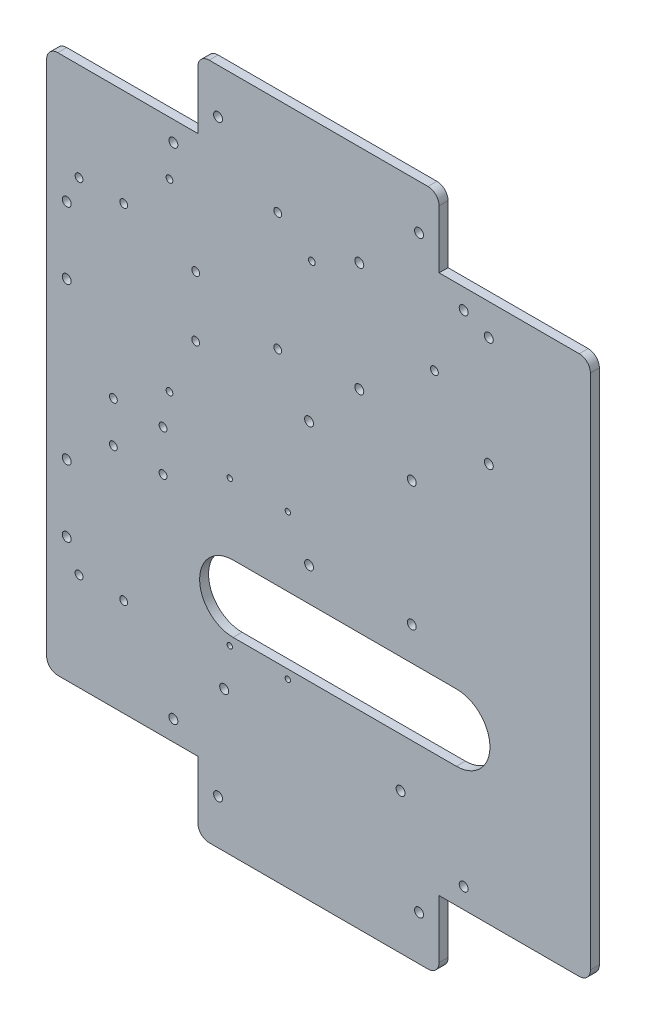
SolidWorks part; units mm, degrees
material "Alliage 1060"
ref_plane "Plan de dessus" through (0, 0, 0) normal (0, 0, 1) x (1, 0, 0)
ref_plane "Plan de droite" through (0, 0, 0) normal (0, 1, 0) x (1, 0, 0)
ref_plane "Plan de face" through (0, 0, 0) normal (1, 0, 0) x (0, 0, -1)
sketch "Esquisse1" plane through (0, 0, 0) normal (0, 0, 1) x (1, 0, 0)
  line L0 (0, 0) -> (-200, 0)
  line L1 (-200, 0) -> (-224.7487, 24.7487)
  line L2 (-224.7487, 24.7487) -> (-224.7487, 284.7487)
  line L3 (-224.7487, 284.7487) -> (-200, 309.4975)
  line L4 (-200, 309.4975) -> (0, 309.4975)
  line L5 (0, 309.4975) -> (24.7487, 284.7487)
  line L6 (24.7487, 284.7487) -> (24.7487, 24.7487)
  line L7 (24.7487, 24.7487) -> (0, 0)
  dimension "D1" = 260
  dimension "D2" = 35
  dimension "D3" = 135
  dimension "D4" = 200
extrude "Base" add sketch "Esquisse1" along normal blind 4
fillet "Congé1" radius 3 8 edges at (-200, 0, 2) (-224.7487, 24.7487, 2) (-224.7487, 284.7487, 2) (-200, 309.4975, 2) (0, 309.4975, 2) (24.7487, 284.7487, 2) (24.7487, 24.7487, 2) (0, 0, 2)
sketch "Esquisse19" plane through (0, 0, 0) normal (0, 0, -1) x (-1, 0, 0)
  line L0 (100, 309.4975) -> (100, 0) construction
  line L1 (1.2426, 309.4975) -> (198.7574, 309.4975) construction
  line L2 (198.7574, 0) -> (1.2426, 0) construction
  line L3 (-24.7487, 154.7487) -> (224.7487, 154.7487) construction
  line L4 (-24.7487, 25.9914) -> (-24.7487, 283.5061) construction
  line L5 (224.7487, 283.5061) -> (224.7487, 25.9914) construction
sketch "Esquisse25" plane through (0, 0, 0) normal (0, 0, -1) x (-1, 0, 0)
  line L0 (-24.7487, 25.9914) -> (-24.7487, 283.5061) construction
  line L1 (-21.7487, 33) -> (45, 33)
  line L2 (-24.7487, 33) -> (-24.7487, 0)
  line L3 (-24.7487, 0) -> (45, 0)
  line L4 (45, 33) -> (45, 3)
  line L5 (198.7574, 0) -> (1.2426, 0) construction
  line L6 (100, 309.4975) -> (100, 0) construction
  line L7 (100, 0) -> (100, 309.4975) construction
  line L8 (-24.7487, 154.7487) -> (224.7487, 154.7487) construction
  line L9 (224.7487, 0) -> (155, 0)
  line L10 (155, 33) -> (155, 3)
  line L11 (221.7487, 33) -> (155, 33)
  line L12 (224.7487, 33) -> (224.7487, 0)
  line L13 (224.7487, 276.4975) -> (224.7487, 309.4975)
  line L14 (221.7487, 276.4975) -> (155, 276.4975)
  line L15 (155, 276.4975) -> (155, 306.4975)
  line L16 (224.7487, 309.4975) -> (155, 309.4975)
  line L17 (-24.7487, 309.4975) -> (45, 309.4975)
  line L18 (45, 276.4975) -> (45, 306.4975)
  line L19 (-21.7487, 276.4975) -> (45, 276.4975)
  line L20 (-24.7487, 276.4975) -> (-24.7487, 309.4975)
  line L22 (45, 309.4975) -> (155, 309.4975)
  line L24 (45, 306.4975) -> (155, 306.4975)
  line L26 (45, 0) -> (155, 0)
  line L28 (45, 3) -> (155, 3)
  line L31 (-24.7487, 276.4975) -> (-24.7487, 33)
  line L33 (-21.7487, 276.4975) -> (-21.7487, 33)
  line L35 (224.7487, 276.4975) -> (224.7487, 33)
  line L37 (221.7487, 276.4975) -> (221.7487, 33)
  dimension "D1" = 55
  dimension "D2" = 33
  dimension "D3" = 3
  dimension "D4" = 3
  dimension "D5" = 3
  dimension "D6" = 3
extrude "Enlèv. mat.-Extru.1" cut sketch "Esquisse25" against normal through all
sketch "Esquisse33" plane through (0, 0, 4) normal (0, 0, 1) x (1, 0, 0)
  line L0 (-207.2487, 231.7487) -> (-187.2487, 231.7487) construction
  line L2 (-221.7487, 33) -> (-221.7487, 276.4975) construction
  line L3 (-221.7487, 154.7487) -> (21.7487, 154.7487) construction
  line L4 (21.7487, 276.4975) -> (21.7487, 33) construction
  line L5 (-100, 306.4975) -> (-100, 3) construction
  line L6 (-155, 306.4975) -> (-45, 306.4975) construction
  line L7 (-45, 3) -> (-155, 3) construction
  circle A0 centre (-207.2487, 231.7487) radius 1.75
  circle A1 centre (-187.2487, 231.7487) radius 1.75
  circle A2 centre (-207.2487, 77.7487) radius 1.75
  circle A3 centre (-187.2487, 77.7487) radius 1.75
  dimension "D3" = 3.5
  dimension "D1" = 20
  dimension "D2" = 14.5
  dimension "D4" = 77
extrude "Percage Main_De_Dieu" cut sketch "Esquisse33" against normal through all
sketch "Esquisse26" plane through (0, 0, 0) normal (0, 0, -1) x (-1, 0, 0)
  line L0 (212.7487, 189.7487) -> (212.7487, 219.7487) construction
  line L1 (221.7487, 33) -> (221.7487, 276.4975) construction
  line L2 (-24.7487, 154.7487) -> (224.7487, 154.7487) construction
  line L3 (224.7487, 154.7487) -> (-24.7487, 154.7487) construction
  line L4 (100, 309.4975) -> (100, 0) construction
  circle A0 centre (212.7487, 189.7487) radius 2
  circle A1 centre (212.7487, 219.7487) radius 2
  circle A2 centre (212.7487, 89.7487) radius 2
  circle A3 centre (212.7487, 119.7487) radius 2
  point P8 (212.7487, 204.7487)
  dimension "D1" = 4
  dimension "D2" = 30
  dimension "D3" = 9
  dimension "D4" = 50
extrude "Percage Buck Converter" cut sketch "Esquisse26" against normal through all
sketch "Esquisse27" plane through (0, 0, 0) normal (0, 0, -1) x (-1, 0, 0)
  line L0 (142.2513, 66) -> (63.2513, 66) construction
  line L1 (-21.7487, 276.4975) -> (-21.7487, 33) construction
  line L2 (-21.7487, 33) -> (45, 33) construction
  circle A0 centre (142.2513, 66) radius 2
  circle A1 centre (63.2513, 66) radius 2
  dimension "D2" = 4
  dimension "D1" = 79
  dimension "D3" = 85
  dimension "D4" = 33
extrude "Percage Teensy Moteur" cut sketch "Esquisse27" against normal through all
sketch "Esquisse28" plane through (0, 0, 0) normal (0, 0, -1) x (-1, 0, 0)
  line L0 (166.7487, 169.0225) -> (166.7487, 251.4975) construction
  line L1 (166.7487, 251.4975) -> (102.9987, 251.4975) construction
  line L2 (224.7487, 154.7487) -> (-24.7487, 154.7487) construction
  line L3 (221.7487, 33) -> (221.7487, 276.4975) construction
  line L4 (221.7487, 276.4975) -> (155, 276.4975) construction
  circle A0 centre (166.7487, 251.4975) radius 1.5
  circle A1 centre (102.9987, 251.4975) radius 1.5
  circle A2 centre (166.7487, 169.0225) radius 1.5
  dimension "D1" = 3
  dimension "D2" = 63.75
  dimension "D3" = 82.475
  dimension "D4" = 55
  dimension "D5" = 25
extrude "Percage Carte Alim" cut sketch "Esquisse28" against normal through all
sketch "Esquisse29" plane through (0, 0, 0) normal (0, 0, -1) x (-1, 0, 0)
  line L0 (221.7487, 33) -> (221.7487, 276.4975) construction
  line L1 (81.7487, 212.4975) -> (23.7487, 212.4975) construction
  line L2 (81.7487, 212.4975) -> (81.7487, 261.4975) construction
  line L3 (81.7487, 261.4975) -> (23.7487, 261.4975) construction
  line L4 (23.7487, 212.4975) -> (23.7487, 261.4975) construction
  line L5 (221.7487, 276.4975) -> (155, 276.4975) construction
  circle A0 centre (81.7487, 212.4975) radius 2
  circle A1 centre (23.7487, 212.4975) radius 2
  circle A2 centre (23.7487, 261.4975) radius 2
  circle A3 centre (81.7487, 261.4975) radius 2
  dimension "D3" = 4
  dimension "D1" = 49
  dimension "D2" = 58
  dimension "D4" = 140
  dimension "D5" = 15
extrude "Percage Rasp" cut sketch "Esquisse29" against normal through all
sketch "Esquisse32" plane through (0, 0, 4) normal (0, 0, 1) x (1, 0, 0)
  line L0 (-118.2513, 262.8275) -> (-118.2513, 209.8275) construction
  line L1 (-48.1113, 236.4975) -> (-118.2513, 236.4975) construction
  line L2 (-45, 276.4975) -> (21.7487, 276.4975) construction
  line L3 (21.7487, 276.4975) -> (21.7487, 33) construction
  circle A0 centre (-118.2513, 262.8275) radius 1.75
  circle A1 centre (-118.2513, 209.8275) radius 1.75
  circle A2 centre (-48.1113, 236.4975) radius 1.75
  dimension "D1" = 3.5
  dimension "D2" = 53
  dimension "D3" = 70.14
  dimension "D4" = 26.33
  dimension "D5" = 40
  dimension "D6" = 140
extrude "Percage Teensy Actionneurs" cut sketch "Esquisse32" against normal through all
sketch "Esquisse30" plane through (0, 0, 0) normal (0, 0, -1) x (-1, 0, 0)
  line L0 (-21.7487, 276.4975) -> (-21.7487, 33) construction
  line L1 (104.2513, 133) -> (58.2513, 133) construction
  line L2 (104.2513, 133) -> (104.2513, 188.8) construction
  line L3 (104.2513, 188.8) -> (58.2513, 188.8) construction
  line L4 (58.2513, 133) -> (58.2513, 188.8) construction
  line L5 (-21.7487, 33) -> (45, 33) construction
  circle A0 centre (104.2513, 133) radius 2
  circle A1 centre (58.2513, 133) radius 2
  circle A2 centre (58.2513, 188.8) radius 2
  circle A3 centre (104.2513, 188.8) radius 2
  dimension "D3" = 4
  dimension "D1" = 55.8
  dimension "D2" = 46
  dimension "D4" = 80
  dimension "D5" = 100
extrude "Percage Alim Actionneurs" cut sketch "Esquisse30" against normal through all
sketch "Esquisse31" plane through (0, 0, 0) normal (0, 0, -1) x (-1, 0, 0)
  line L0 (138.2513, 103) -> (38.2513, 103) construction
  line L1 (138.2513, 88) -> (38.2513, 88)
  line L2 (138.2513, 118) -> (38.2513, 118)
  line L3 (-21.7487, 33) -> (45, 33) construction
  line L4 (-21.7487, 276.4975) -> (-21.7487, 33) construction
  arc A0 (138.2513, 88) -> (138.2513, 118) centre (138.2513, 103) ccw
  arc A1 (38.2513, 118) -> (38.2513, 88) centre (38.2513, 103) ccw
  point P2 (88.2513, 103)
  dimension "D2" = 15
  dimension "D1" = 100
  dimension "D3" = 70
  dimension "D4" = 60
extrude "Perçage Fils" cut sketch "Esquisse31" against normal through all
sketch "Esquisse34" plane through (0, 0, 0) normal (0, 0, -1) x (-1, 0, 0)
  line L0 (221.7487, 154.7487) -> (-21.7487, 154.7487) construction
  line L1 (221.7487, 33) -> (221.7487, 276.4975) construction
  line L2 (-21.7487, 276.4975) -> (-21.7487, 33) construction
  line L3 (191.8737, 153.9) -> (169.6237, 153.9) construction
  line L4 (169.6237, 135.5) -> (191.8737, 135.5) construction
  line L5 (100, 306.4975) -> (100, 3) construction
  line L6 (155, 306.4975) -> (45, 306.4975) construction
  line L7 (45, 3) -> (155, 3) construction
  line L8 (155, 33) -> (221.7487, 33) construction
  circle A2 centre (169.6237, 153.9) radius 1.75
  circle A3 centre (191.8737, 153.9) radius 1.75
  circle A4 centre (169.6237, 135.5) radius 1.75
  circle A5 centre (191.8737, 135.5) radius 1.75
  point P12 (180.7487, 153.9)
  dimension "D2" = 3.5
  dimension "D5" = 102.5
  dimension "D3" = 22.25
  dimension "D4" = 41
  dimension "D7" = 18.4
extrude "Perçage Moteur Ascenseur" cut sketch "Esquisse34" against normal through all
sketch "Esquisse35" plane through (0, 0, 4) normal (0, 0, 1) x (1, 0, 0)
  line L0 (-155, 33) -> (-221.7487, 33) construction
  line L1 (-139.7487, 149) -> (-113.7487, 149) construction
  line L2 (-139.7487, 149) -> (-139.7487, 84) construction
  line L3 (-139.7487, 84) -> (-113.7487, 84) construction
  line L4 (-113.7487, 149) -> (-113.7487, 84) construction
  line L5 (-221.7487, 33) -> (-221.7487, 276.4975) construction
  circle A0 centre (-139.7487, 149) radius 1.2
  circle A1 centre (-113.7487, 149) radius 1.2
  circle A2 centre (-113.7487, 84) radius 1.2
  circle A3 centre (-139.7487, 84) radius 1.2
  dimension "D3" = 2.4
  dimension "D1" = 26
  dimension "D2" = 65
  dimension "D4" = 51
  dimension "80" = 82
extrude "Perçage Driver Ascenseur" cut sketch "Esquisse35" against normal through all
sketch "Esquisse36" plane through (0, 0, 4) normal (0, 0, 1) x (1, 0, 0)
  line L0 (-155, 33) -> (-155, 144.3181) construction
  line L2 (-221.7487, 276.4975) -> (-155, 276.4975) construction
  circle A0 centre (-155, 194.4975) radius 1.75
  circle A1 centre (-155, 221.4975) radius 1.75
  dimension "D3" = 3.5
  dimension "D1" = 27
  dimension "D2" = 55
extrude "Enlèv. mat.-Extru.2" cut sketch "Esquisse36" against normal blind 5
sketch "Esquisse39" plane through (0, 0, 4) normal (0, 0, 1) x (1, 0, 0)
  line L0 (-100, 306.4975) -> (-100, 3) construction
  line L1 (-155, 276.4975) -> (-145, 276.4975) construction
  line L2 (-155, 276.4975) -> (-155, 286.4975) construction
  line L3 (-155, 286.4975) -> (-145, 286.4975) construction
  line L4 (-145, 276.4975) -> (-145, 286.4975) construction
  line L5 (-155, 276.4975) -> (-165, 276.4975) construction
  line L6 (-155, 276.4975) -> (-155, 266.4975) construction
  line L7 (-155, 266.4975) -> (-165, 266.4975) construction
  line L8 (-165, 276.4975) -> (-165, 266.4975) construction
  line L9 (-155, 306.4975) -> (-45, 306.4975) construction
  line L10 (-45, 3) -> (-155, 3) construction
  line L11 (-221.7487, 154.7487) -> (21.7487, 154.7487) construction
  line L12 (-221.7487, 33) -> (-221.7487, 276.4975) construction
  line L13 (21.7487, 276.4975) -> (21.7487, 33) construction
  circle A0 centre (-145, 286.4975) radius 2
  circle A1 centre (-165, 266.4975) radius 2
  circle A2 centre (-35, 266.4975) radius 2
  circle A3 centre (-55, 286.4975) radius 2
  circle A4 centre (-35, 43) radius 2
  circle A5 centre (-55, 23) radius 2
  circle A6 centre (-165, 43) radius 2
  circle A7 centre (-145, 23) radius 2
  point P24 (0, 0)
  dimension "D3" = 4
  dimension "D1" = 10
  dimension "D2" = 10
extrude "Perçage Equerre" cut sketch "Esquisse39" against normal through all
sketch "Esquisse38" plane through (0, 0, 0) normal (0, 0, -1) x (-1, 0, 0)
  line L0 (-21.7487, 33) -> (45, 33) construction
  line L1 (-21.7487, 3) -> (46, 3)
  line L2 (-21.7487, 3) -> (-21.7487, 34)
  line L3 (-21.7487, 34) -> (46, 34)
  line L4 (46, 3) -> (46, 34)
  line L5 (45, 33) -> (45, 3) construction
  line L6 (45, 3) -> (155, 3) construction
  line L7 (-21.7487, 276.4975) -> (-21.7487, 33) construction
  line L8 (221.7487, 33) -> (221.7487, 276.4975) construction
  line L9 (221.7487, 3) -> (154, 3)
  line L10 (221.7487, 3) -> (221.7487, 34)
  line L11 (221.7487, 34) -> (154, 34)
  line L12 (154, 3) -> (154, 34)
  line L15 (155, 306.4975) -> (45, 306.4975) construction
  line L16 (221.7487, 306.4975) -> (154, 306.4975)
  line L17 (221.7487, 306.4975) -> (221.7487, 275.4975)
  line L18 (221.7487, 275.4975) -> (154, 275.4975)
  line L19 (154, 306.4975) -> (154, 275.4975)
  line L20 (-21.7487, 306.4975) -> (46, 306.4975)
  line L21 (-21.7487, 306.4975) -> (-21.7487, 275.4975)
  line L22 (-21.7487, 275.4975) -> (46, 275.4975)
  line L23 (46, 306.4975) -> (46, 275.4975)
  dimension "D1" = 1
  dimension "D2" = 1
extrude "Enlèv. mat.-Extru.3" cut sketch "Esquisse38" against normal through all
fillet "Congé2" radius 5 8 edges at (-221.7487, 275.4975, 2) (-154, 306.4975, 2) (-46, 306.4975, 2) (21.7487, 275.4975, 2) (-221.7487, 34, 2) (-154, 3, 2) (-46, 3, 2) (21.7487, 34, 2)
